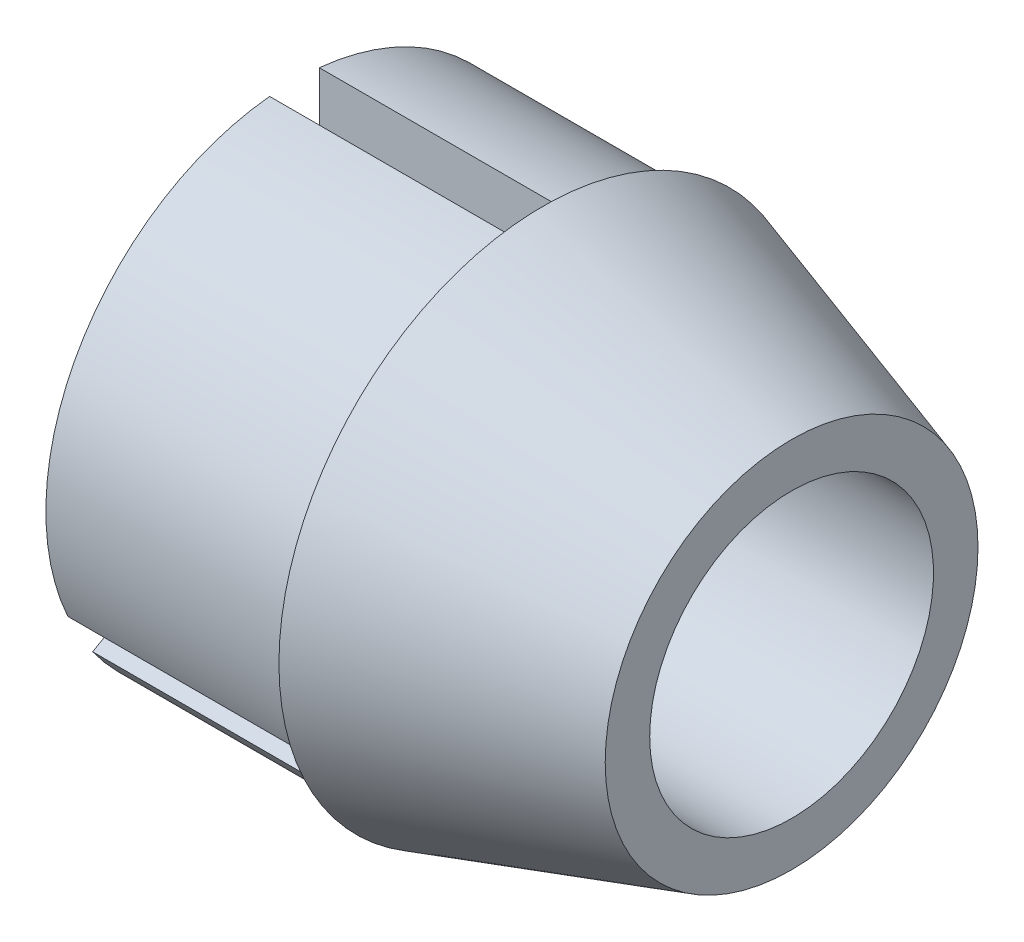
SolidWorks part; units mm, degrees
ref_plane "Front Plane" through (0, 0, 0) normal (0, 0, 1) x (1, 0, 0)
ref_plane "Top Plane" through (0, 0, 0) normal (0, 1, 0) x (1, 0, 0)
ref_plane "Right Plane" through (0, 0, 0) normal (1, 0, 0) x (0, 0, -1)
sketch "Sketch1" plane through (0, 0, 0) normal (0, 0, 1) x (1, 0, 0)
  line L0 (0, 14.5) -> (25.4, 14.5)
  line L1 (0, 14.5) -> (0, 26.9875) construction
  line L2 (0, 26.9875) -> (25.4, 19.0466)
  line L3 (25.4, 19.0466) -> (25.4, 14.5)
  line L4 (0, 26.9875) -> (0, 25.4)
  line L5 (0, 25.4) -> (-25.4, 25.4)
  line L6 (-25.4, 25.4) -> (-25.4, 16.51)
  line L7 (-25.4, 16.51) -> (0, 16.51)
  line L8 (0, 16.51) -> (0, 14.5)
  dimension "D1" = 25.4
  dimension "D2" = 4.5466
  dimension "D3" = 26.9875
  dimension "D4" = 14.5
  dimension "D5" = 1.5875
  dimension "D6" = 16.51
  dimension "D7" = 25.4
ref_axis "Axis1" through (-1.27, 0, 0) along (1, 0, 0)
revolve "Revolve1" add sketch "Sketch1" angle 360 about axis through (-1.27, 0, 0) along (1, 0, 0)
sketch "Sketch2" plane through (-25.4, 0, 0) normal (-1, 0, 0) x (0, 0, 1)
  line L0 (28.7663, -13.6753) -> (6.7693, -0.9753)
  line L1 (-2.54, 31.75) -> (2.54, 31.75)
  line L2 (-2.54, 31.75) -> (-2.54, 6.35)
  line L3 (-2.54, 6.35) -> (2.54, 6.35)
  line L4 (2.54, 31.75) -> (2.54, 6.35)
  line L5 (-2.54, 31.75) -> (2.54, 6.35) construction
  line L6 (-2.54, 6.35) -> (2.54, 31.75) construction
  line L7 (28.7663, -13.6753) -> (26.2263, -18.0747)
  line L8 (26.2263, -18.0747) -> (4.2293, -5.3747)
  line L9 (6.7693, -0.9753) -> (4.2293, -5.3747)
  line L10 (-26.2263, -18.0747) -> (-4.2293, -5.3747)
  line L11 (-26.2263, -18.0747) -> (-28.7663, -13.6753)
  line L12 (-28.7663, -13.6753) -> (-6.7693, -0.9753)
  line L13 (-4.2293, -5.3747) -> (-6.7693, -0.9753)
  point P0 (0, 19.05)
  point P16 (0, 0)
  dimension "D1" = 5.08
  dimension "D2" = 25.4
  dimension "D3" = 6.35
  dimension "D4" = 3
extrude "Cut-Extrude1" cut sketch "Sketch2" against normal up to surface (25.4 mm away) up to face at (0, 0, 25.4)
